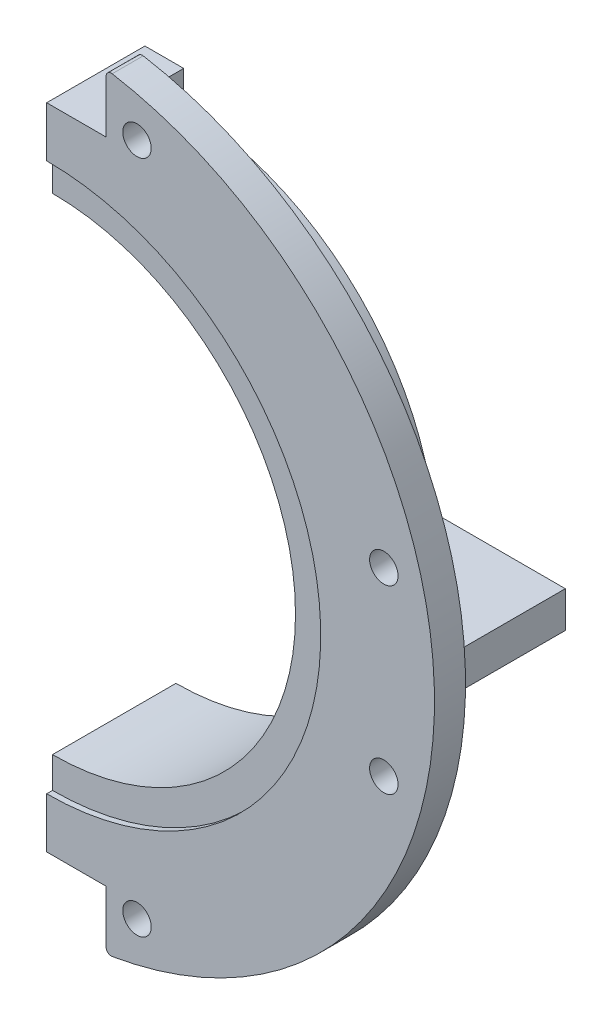
SolidWorks part; units mm, degrees
ref_plane "Front" through (0, 0, 0) normal (0, 0, 1) x (1, 0, 0)
ref_plane "Top" through (0, 0, 0) normal (0, 1, 0) x (1, 0, 0)
ref_plane "Right" through (0, 0, 0) normal (1, 0, 0) x (0, 0, -1)
sketch "Sketch1" plane through (0, 0, 0) normal (0, 0, 1) x (1, 0, 0)
  line L1 (0, 0) -> (180, 0)
  line L2 (0, 0) -> (0, 180)
  line L3 (0, 180) -> (180, 180)
  line L4 (180, 0) -> (180, 180)
  dimension "D1" = 180
extrude "Boss-Extrude1" add sketch "Sketch1" along normal blind 6
sketch "Sketch2" plane through (0, 0, 0) normal (0, 0, -1) x (-1, 0, 0)
  line L0 (0, 90) -> (-180, 90) construction
  line L1 (0, 180) -> (0, 0) construction
  line L3 (-180, 0) -> (-180, 180) construction
  circle A0 centre (-90, 90) radius 46.3
  circle A1 centre (-90, 90) radius 50.3
  point P11 (-90, 90)
  dimension "D1" = 92.6
  dimension "D2" = 4
extrude "Boss-Extrude2" add sketch "Sketch2" along normal blind 19
sketch "Sketch3" plane through (0, 0, 0) normal (0, 0, -1) x (-1, 0, 0)
  circle A0 centre (-90, 90) radius 47
  dimension "D1" = 94
extrude "Cut-Extrude1" cut sketch "Sketch3" against normal through all both and the other way through all
sketch "Sketch4" plane through (0, 0, 0) normal (0, 0, -1) x (-1, 0, 0)
  line L0 (0, 77.5) -> (0, 102.5)
  line L1 (0, 180) -> (0, 0) construction
  line L2 (0, 77.5) -> (-41.2779, 77.5)
  line L3 (0, 102.5) -> (-41.2779, 102.5)
  circle A0 centre (-90, 90) radius 50.3 construction
  arc A1 (-41.2779, 77.5) -> (-41.2779, 102.5) centre (-90, 90) ccw
  point P2 (0, 90)
  point P5 (0, 90)
  dimension "D1" = 25
extrude "Boss-Extrude3" add sketch "Sketch4" along normal blind 60
ref_plane "Plane1" through (0, 90, 0) normal (0, -1, 0) x (-1, 0, 0)
fillet "Fillet4" radius 3 2 edges at (41.2779, 77.5, -9.5) (41.2779, 102.5, -9.5)
hole_wizard "M5 Clearance Hole1" positions "Sketch11" profile "Sketch12" hole size "M5" standard "ANSI Metric" end condition up to next
sketch "Sketch11" plane through (0, 0, 0) normal (0, 0, -1) x (-1, 0, 0)
  point P52 (-107.4703, 155.2)
  point P58 (-155.2, 107.4703)
  point P61 (-155.2, 72.5297)
  point P67 (-107.4703, 24.8)
  point P70 (-72.5297, 24.8)
  point P76 (-24.8, 72.5297)
  point P79 (-24.8, 107.4703)
  point P85 (-72.5297, 155.2)
sketch "Sketch12" plane through (107.4703, 155.2, 0) normal (1, 0, 0) x (0, 1, 0)
  line L0 (0, 0) -> (0, 6)
  line L1 (0, 6) -> (2.75, 6)
  line L2 (2.75, 6) -> (2.75, 0)
  line L5 (2.75, 0) -> (0, 0)
  line L11 (0, -6.35) -> (0, 107.95) construction
  dimension "Thru Hole Dia." = 5.5
  dimension "Thru Hole Depth" = 6
sketch "Sketch15" plane through (0, 0, 0) normal (0, 0, -1) x (-1, 0, 0)
  line L0 (-180, 90) -> (-90, 90) construction
  line L3 (-180, 0) -> (-180, 180) construction
  line L4 (-137.3, 93.5) -> (-137.3, 86.5)
  line L5 (-137.3, 93.5) -> (-162.3, 93.5)
  line L6 (-162.3, 93.5) -> (-162.3, 86.5)
  line L7 (-137.3, 86.5) -> (-162.3, 86.5)
  line L8 (-93.5, 42.7) -> (-86.5, 36.7) construction
  line L9 (-93.5, 36.7) -> (-86.5, 42.7) construction
  arc A0 (-41.8739, 104.6276) -> (-41.8739, 75.3724) centre (-90, 90) ccw construction
  point P4 (-137.3, 90)
  point P6 (-90, 39.7)
  dimension "D1" = 7
  dimension "D2" = 25
  dimension "D3" = 47.3
extrude "Boss-Extrude5" add sketch "Sketch15" along normal blind 19
ref_plane "Plane2" through (0, 90, 0) normal (0, 1, 0) x (0, 0, -1)
sketch "Sketch17" plane through (0, 90, 0) normal (0, 1, 0) x (0, 0, -1)
  line L6 (-1.0441, -134.6888) -> (19, -154.733)
  line L8 (19, -140.1781) -> (19, -162.3) construction
  line L9 (19, -154.733) -> (19, -159.233)
  line L10 (19, -159.233) -> (-5.5441, -134.6888)
  line L11 (-5.5441, -134.6888) -> (-1.0441, -134.6888)
  dimension "D1" = 4.5
  dimension "D2" = 4.5
extrude "Cut-Extrude3" cut sketch "Sketch17" against normal mid plane 4 contours L6 L9 L10 | L11 L10 L9 L6 region at (145.8738, 90, -7.8151)
fillet "Fillet5" radius 1.5 4 edges at (145.8452, 92, -10.1122) (145.8452, 88, -10.1122) (148.0952, 92, -7.8622) (148.0952, 88, -7.8622)
sketch "Sketch30" plane through (0, 90, 0) normal (0, -1, 0) x (-1, 0, 0)
  line L1 (22.1625, 78.3225) -> (-206.3555, 78.3225)
  line L2 (22.1625, 78.3225) -> (22.1625, -34.6262)
  line L3 (22.1625, -34.6262) -> (-206.3555, -34.6262)
  line L4 (-206.3555, 78.3225) -> (-206.3555, -34.6262)
sketch "Sketch31" plane through (0, 0, 6) normal (0, 0, 1) x (1, 0, 0)
  line L2 (0, 180) -> (0, 0) construction
  line L3 (0, 0) -> (180, 0) construction
  line L4 (180, 0) -> (180, 180) construction
  line L5 (180, 180) -> (0, 180) construction
  line L8 (0, 180) -> (0, 102.5)
  line L9 (0, 0) -> (180, 0)
  line L10 (180, 0) -> (180, 180)
  line L11 (180, 180) -> (0, 180)
  line L12 (0, 77.5) -> (0, 0)
  line L13 (41.2779, 77.5) -> (0, 77.5) construction
  line L14 (0, 102.5) -> (41.2779, 102.5) construction
  line L15 (16.049, 77.5) -> (0, 77.5)
  line L16 (0, 102.5) -> (16.049, 102.5)
  circle A4 centre (90, 90) radius 75 construction
  arc A5 (16.049, 77.5) -> (16.049, 102.5) centre (90, 90) ccw
extrude "Cut-Extrude4" cut sketch "Sketch31" against normal up to next contours A5 L16 L8 L11 L10 L9 L12 L15
sketch "Sketch33" plane through (0, 0, 6) normal (0, 0, 1) x (1, 0, 0)
  line L1 (0, 102.5) -> (1, 102.5)
  line L2 (0, 102.5) -> (0, 77.5)
  line L3 (0, 77.5) -> (1, 77.5)
  line L4 (1, 102.5) -> (1, 77.5)
  dimension "D1" = 1
extrude "Cut-Extrude5" cut sketch "Sketch33" against normal up to next
sketch "Sketch35" plane through (0, 0, 0) normal (0, 0, -1) x (-1, 0, 0)
  line L0 (-90, 15) -> (-90, 165) construction
  line L4 (-97.5, 152.7377) -> (-82.5, 152.7377)
  line L5 (-97.5, 152.7377) -> (-97.5, 139.7377)
  line L6 (-97.5, 139.7377) -> (-82.5, 139.7377)
  line L7 (-82.5, 152.7377) -> (-82.5, 139.7377)
  line L8 (-97.5, 40.2623) -> (-82.5, 40.2623)
  line L9 (-97.5, 40.2623) -> (-97.5, 27.2623)
  line L10 (-97.5, 27.2623) -> (-82.5, 27.2623)
  line L11 (-82.5, 40.2623) -> (-82.5, 27.2623)
  arc A0 (-16.049, 102.5) -> (-16.049, 77.5) centre (-90, 90) ccw construction
  arc A1 (-41.8739, 104.6276) -> (-140.1781, 93.5) centre (-90, 90) ccw construction
  arc A2 (-140.1781, 86.5) -> (-41.8739, 75.3724) centre (-90, 90) ccw construction
  point P8 (-90, 90)
  point P18 (-90, 152.7377)
  point P26 (-90, 27.2623)
  dimension "D1" = 15
  dimension "D2" = 13
  dimension "D3" = 13
  dimension "D4" = 15
extrude "Boss-Extrude6" add sketch "Sketch35" along normal blind 13
hole_wizard "M5 Clearance Hole2" positions "Sketch38" profile "Sketch39" hole size "M5" standard "ANSI Metric" end condition through all
sketch "Sketch38" plane through (97.5, 0, 0) normal (1, 0, 0) x (0, 0, -1)
  line L0 (13, 152.7377) -> (0, 152.7377) construction
  line L1 (13, 40.2623) -> (13, 27.2623) construction
  line L2 (13, 152.7377) -> (13, 139.7377) construction
  point P0 (6.5, 146.2377)
  point P3 (6.5, 33.7623)
  point P8 (6.5, 152.7377)
  point P12 (13, 33.7623)
  point P15 (13, 146.2377)
sketch "Sketch39" plane through (97.5, 146.2377, -6.5) normal (0, 1, 0) x (0, 0, -1)
  line L0 (0, 0) -> (0, 96.5)
  line L1 (0, 96.5) -> (2.75, 96.5)
  line L2 (2.75, 96.5) -> (2.75, 0)
  line L5 (2.75, 0) -> (0, 0)
  line L11 (0, -6.35) -> (0, 107.95) construction
  dimension "Thru Hole Dia." = 5.5
  dimension "Thru Hole Depth" = 96.5
sketch "Sketch40" plane through (82.5, 0, 0) normal (-1, 0, 0) x (0, 0, 1)
  line L0 (-13, 139.7377) -> (-13, 152.7377) construction
  line L1 (-10.75, 143.784) -> (-6.5, 141.3302)
  line L2 (-6.5, 141.3302) -> (-2.25, 143.784)
  line L3 (-2.25, 143.784) -> (-2.25, 148.6915)
  line L4 (-2.25, 148.6915) -> (-6.5, 151.1452)
  line L5 (-6.5, 151.1452) -> (-10.75, 148.6915)
  line L6 (-10.75, 148.6915) -> (-10.75, 143.784)
  line L7 (-13, 27.2623) -> (-13, 139.7377) construction
  line L8 (-2.25, 31.3085) -> (-2.25, 36.216)
  line L9 (-2.25, 36.216) -> (-6.5, 38.6698)
  line L10 (-6.5, 38.6698) -> (-10.75, 36.216)
  line L11 (-10.75, 36.216) -> (-10.75, 31.3085)
  line L12 (-10.75, 31.3085) -> (-6.5, 28.8548)
  line L13 (-6.5, 28.8548) -> (-2.25, 31.3085)
  circle A0 centre (-6.5, 146.2377) radius 4.25 construction
  circle A1 centre (-6.5, 33.7623) radius 4.25 construction
  dimension "D1" = 8.5
  dimension "D2" = 8.5
extrude "Cut-Extrude6" cut sketch "Sketch40" against normal blind 4.2
sketch "Sketch41" plane through (0, 0, 0) normal (0, 0, -1) x (-1, 0, 0)
  line L0 (-90, 15) -> (-90, 165) construction
  line L2 (22.1625, 90) -> (-206.3555, 90) construction
  line L3 (-101.5, 152.7377) -> (-78.5, 152.7377)
  line L4 (-101.5, 152.7377) -> (-101.5, 167.7377)
  line L5 (-101.5, 167.7377) -> (-78.5, 167.7377)
  line L6 (-78.5, 152.7377) -> (-78.5, 167.7377)
  line L7 (-14.4828, 90) -> (-165.5172, 90) construction
  line L8 (-78.5, 27.2623) -> (-78.5, 12.2623)
  line L9 (-101.5, 12.2623) -> (-78.5, 12.2623)
  line L10 (-101.5, 27.2623) -> (-101.5, 12.2623)
  line L11 (-101.5, 27.2623) -> (-78.5, 27.2623)
  line L14 (-82.5, 152.7377) -> (-97.5, 152.7377) construction
  arc A0 (-16.049, 102.5) -> (-16.049, 77.5) centre (-90, 90) ccw construction
  point P7 (-90, 90)
  point P15 (-90, 152.7377)
  point P24 (-90, 90)
  dimension "D1" = 15
  dimension "D2" = 23
extrude "Cut-Extrude7" cut sketch "Sketch41" against normal up to next
fillet "Fillet8" radius 1 4 edges at (101.5, 164.1131, 3) (78.5, 164.1131, 3) (101.5, 15.8869, 3) (78.5, 15.8869, 3)
sketch "Sketch42" plane through (0, 102.5, 0) normal (0, 1, 0) x (1, 0, 0)
  line L0 (15, -6) -> (1, 24)
  line L1 (165, -6) -> (15, -6) construction
  line L2 (1, -6) -> (16.049, -6) construction
  line L3 (1, 60) -> (1, -6) construction
  line L4 (1, 24) -> (1, -6)
  line L5 (1, -6) -> (15, -6)
  dimension "D1" = 30
  dimension "D2" = 14
extrude "Cut-Extrude8" cut sketch "Sketch42" against normal up to next
ref_plane "Plane3" through (90, 0, 0) normal (1, 0, 0) x (0, 0, -1)
sketch "Sketch43" plane through (90, 0, 0) normal (1, 0, 0) x (0, 0, -1)
  line L1 (-26.2287, 173.6103) -> (66.8607, 173.6103)
  line L2 (-26.2287, 173.6103) -> (-26.2287, 11.2507)
  line L3 (-26.2287, 11.2507) -> (66.8607, 11.2507)
  line L4 (66.8607, 173.6103) -> (66.8607, 11.2507)
sketch "Sketch46" plane through (0, 0, 0) normal (0, 0, -1) x (-1, 0, 0)
  line L0 (-101.5, 162.9366) -> (-101.5, 172.9366)
  line L1 (-101.5, 172.9366) -> (-111.5, 172.9366)
  line L2 (-111.5, 172.9366) -> (-111.5, 161.8523)
  line L9 (-101.5, 152.7377) -> (-101.5, 162.9366)
  line L10 (-101.5, 17.0634) -> (-101.5, 27.2623)
  line L11 (-101.5, 27.2623) -> (-97.5, 27.2623)
  line L12 (-97.5, 27.2623) -> (-97.5, 40.2623)
  line L13 (-140.1781, 86.5) -> (-162.3, 86.5)
  line L14 (-162.3, 86.5) -> (-162.3, 93.5)
  line L15 (-162.3, 93.5) -> (-140.1781, 93.5)
  line L16 (-97.5, 139.7377) -> (-97.5, 152.7377)
  line L17 (-97.5, 152.7377) -> (-101.5, 152.7377)
  line L18 (-101.5, 152.7377) -> (-101.5, 162.9366)
  line L19 (-101.5, 17.0634) -> (-101.5, 27.2623)
  line L20 (-101.5, 27.2623) -> (-97.5, 27.2623)
  line L21 (-97.5, 27.2623) -> (-97.5, 40.2623)
  line L22 (-140.1781, 86.5) -> (-162.3, 86.5)
  line L23 (-162.3, 86.5) -> (-162.3, 93.5)
  line L24 (-162.3, 93.5) -> (-140.1781, 93.5)
  line L25 (-97.5, 139.7377) -> (-97.5, 152.7377)
  line L26 (-97.5, 152.7377) -> (-101.5, 152.7377)
  arc A5 (-101.5, 162.9366) -> (-102.6689, 163.9222) centre (-102.5, 162.9366) ccw
  arc A6 (-102.6689, 163.9222) -> (-102.6689, 16.0778) centre (-90, 90) ccw
  arc A7 (-102.6689, 16.0778) -> (-101.5, 17.0634) centre (-102.5, 17.0634) ccw
  arc A8 (-140.1781, 86.5) -> (-97.5, 40.2623) centre (-90, 90) ccw
  arc A9 (-97.5, 139.7377) -> (-140.1781, 93.5) centre (-90, 90) ccw
  arc A10 (-101.5, 162.9366) -> (-102.6689, 163.9222) centre (-102.5, 162.9366) ccw
  arc A11 (-102.6689, 163.9222) -> (-102.6689, 16.0778) centre (-90, 90) ccw
  arc A12 (-102.6689, 16.0778) -> (-101.5, 17.0634) centre (-102.5, 17.0634) ccw
  arc A13 (-140.1781, 86.5) -> (-97.5, 40.2623) centre (-90, 90) ccw
  arc A14 (-97.5, 139.7377) -> (-140.1781, 93.5) centre (-90, 90) ccw
  arc M18 (-101.5, 162.9366) -> (-102.6689, 163.9222) centre (-102.5, 162.9366) ccw
  arc M19 (-102.6689, 163.9222) -> (-102.6689, 16.0778) centre (-90, 90) ccw
  dimension "D2" = 10
  dimension "D3" = 10
  dimension "D1" = 0
extrude "Boss-Extrude8" [suppressed] add sketch "Sketch46" against normal up to surface (6 mm away) contours L1 L2 L0 M19 M18
ref_plane "Plane5" [suppressed] through (90, 0, 0) normal (1, 0, 0) x (0, 0, -1)
mirror "Mirror2" [suppressed] about plane through (90, 0, 0) normal (1, 0, 0)
ref_plane "Plane4" [suppressed] through (0, 90, 0) normal (0, 1, 0) x (1, 0, 0)
mirror "Mirror1" [suppressed] about plane through (0, 90, 0) normal (0, 1, 0)
fillet "Fillet10" [suppressed] radius 1
sketch "Sketch47" plane through (0, 0, 6) normal (0, 0, 1) x (1, 0, 0)
  circle A0 centre (90, 90) radius 53
  circle A1 centre (90, 90) radius 47 construction
  point P3 (0, 0)
  dimension "D1" = 106
extrude "Cut-Extrude10" cut sketch "Sketch47" against normal blind 1.12
ref_plane "Plane6" through (0, 0, -5) normal (0, 0, 1) x (1, 0, 0)
sketch "Sketch51" plane through (0, 0, -13) normal (0, 0, -1) x (-1, 0, 0)
  line L0 (-82.5, 152.7377) -> (-97.5, 152.7377) construction
  line L1 (60, 190) -> (-90, 190)
  line L2 (60, 190) -> (60, -10)
  line L3 (60, -10) -> (-90, -10)
  line L4 (-90, 190) -> (-90, -10)
  line L5 (-162.3, 93.5) -> (-162.3, 86.5) construction
  point P6 (-90, 152.7377)
  point P7 (-162.3, 90)
  point P10 (-90, 90)
  dimension "D1" = 150
  dimension "D2" = 200
extrude "Cut-Extrude12" cut sketch "Sketch51" against normal through all both and the other way through all
sketch "Sketch52" plane through (0, 0, -19) normal (0, 0, -1) x (-1, 0, 0)
  line L1 (-162.3, 86.5) -> (-137.3, 86.5)
  line L2 (-162.3, 86.5) -> (-162.3, 93.5)
  line L3 (-162.3, 93.5) -> (-137.3, 93.5)
  line L4 (-137.3, 86.5) -> (-137.3, 93.5)
  line L5 (-161.3, 87.5) -> (-138.3, 87.5)
  line L6 (-161.3, 87.5) -> (-161.3, 92.5)
  line L7 (-161.3, 92.5) -> (-138.3, 92.5)
  line L8 (-138.3, 87.5) -> (-138.3, 92.5)
  dimension "D1" = 7
  dimension "D2" = 25
  dimension "D3" = 5
  dimension "D4" = 23
  dimension "D5" = 1
  dimension "D6" = 1
extrude "Boss-Extrude9" add sketch "Sketch52" along normal blind 3
chamfer "Chamfer1" distance 1 angle 45 4 edges at (161.3, 90, -22) (149.8, 92.5, -22) (149.8, 87.5, -22) (138.3, 90, -22)
